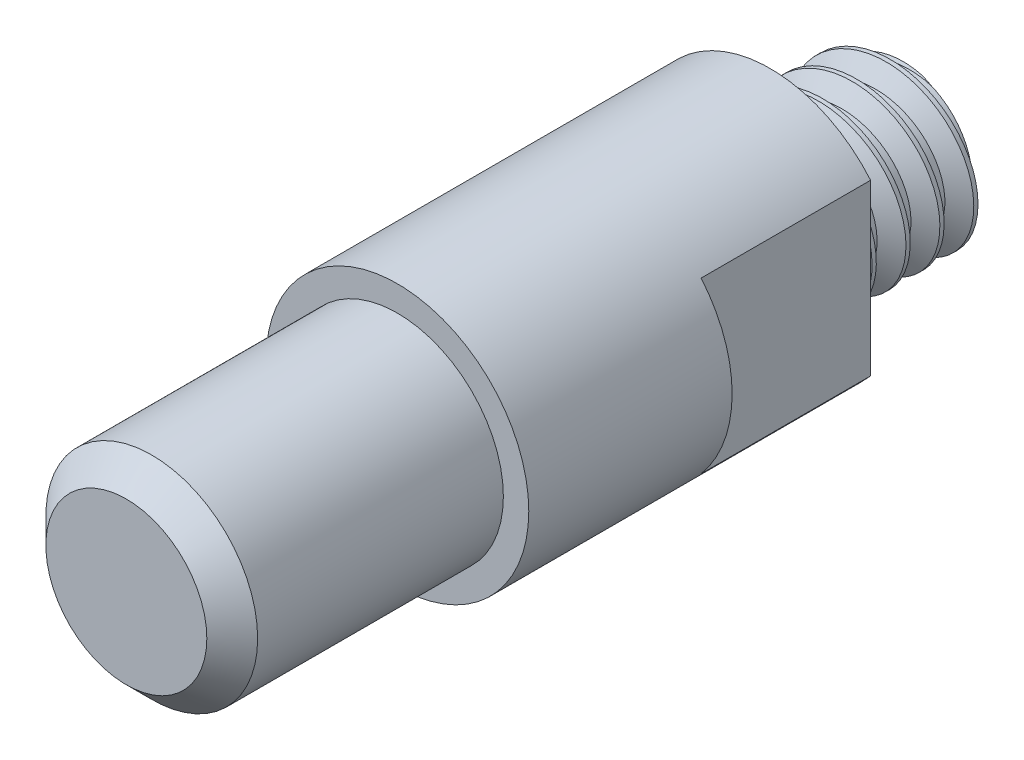
SolidWorks part; units mm, degrees
ref_plane "Front Plane" through (0, 0, 0) normal (1, 0, 0) x (0, 1, 0)
ref_plane "Top Plane" through (0, 0, 0) normal (0, 0, 1) x (0, 1, 0)
ref_plane "Right Plane" through (0, 0, 0) normal (0, 1, 0) x (-1, 0, 0)
sketch "Sketch1" plane through (0, 0, 0) normal (0, 0, 1) x (0, 1, 0)
  circle A0 centre (0, 0) radius 5
  dimension "D1" = 10
extrude "Boss-Extrude1" add sketch "Sketch1" along normal blind 8
thread "Thread1" pitch 2 method cut trim with end face yes profile "Thread Profile1" start angle 0, offset 3, length 13, pitch 2, diameter 10
ref_plane "Plane1" through (5, 0, -3) normal (0, -1, 0) x (1, 0, 0)
sketch "Thread Profile1" plane through (5, 0, -3) normal (0, -1, 0) x (1, 0, 0)
  line L0 (0, 0) -> (0, 2) construction
  line L11 (0, 0) -> (0, 1.75)
  line L12 (0, 1.75) -> (-1.0825, 1.125)
  line L13 (-1.0825, 1.125) -> (-1.0825, 0.625)
  line L15 (-1.0825, 0.625) -> (0, 0)
  line L17 (-1.0825, 0.875) -> (0, 0.875) construction
  point P2 (0, 0)
  dimension "Pitch" = 2
  dimension "Profile_Angle" = 60
  dimension "Profile_Land" = 0.5
  dimension "Profile_Height" = 1.0825
sketch "Sketch4" plane through (0, 0, 0) normal (0, 0, -1) x (1, 0, 0)
  circle A0 centre (0, 0) radius 4
  dimension "D1" = 8
extrude "Cut-Extrude1" cut sketch "Sketch4" against normal blind 10 draft 60 flip side to cut
sketch "Sketch5" plane through (0, 0, 8) normal (0, 0, 1) x (1, 0, 0)
  circle A0 centre (0, 0) radius 7.75
  dimension "D1" = 15.5
extrude "Boss-Extrude2" add sketch "Sketch5" along normal blind 22
sketch "Sketch6" plane through (0, 0, 30) normal (0, 0, 1) x (1, 0, 0)
  circle A0 centre (0, 0) radius 6.25
  dimension "D1" = 12.5
extrude "Boss-Extrude3" add sketch "Sketch6" along normal blind 16
sketch "Sketch7" plane through (0, 0, 8) normal (0, 0, -1) x (1, 0, 0)
  line L1 (-5.9214, -5) -> (5.9214, -5) construction
  line L2 (-5.9214, -5) -> (-5.9214, 5)
  line L3 (-5.9214, 5) -> (5.9214, 5) construction
  line L4 (5.9214, -5) -> (5.9214, 5)
  line L5 (-5.9214, -5) -> (5.9214, 5) construction
  line L6 (-5.9214, 5) -> (5.9214, -5) construction
  circle A1 centre (0, 0) radius 7.75 construction
  arc A2 (-5.9214, 5) -> (-5.9214, -5) centre (0, 0) ccw
  arc A3 (5.9214, 5) -> (-5.9214, 5) centre (0, 0) ccw construction
  arc A4 (-5.9214, -5) -> (5.9214, -5) centre (0, 0) ccw construction
  arc A5 (5.9214, -5) -> (5.9214, 5) centre (0, 0) ccw
  point P0 (0, 0)
  dimension "D1" = 10
extrude "Cut-Extrude2" cut sketch "Sketch7" against normal blind 10
chamfer "Chamfer1" distance 1.5 angle 45 1 edges at (6.25, 0, 46)
